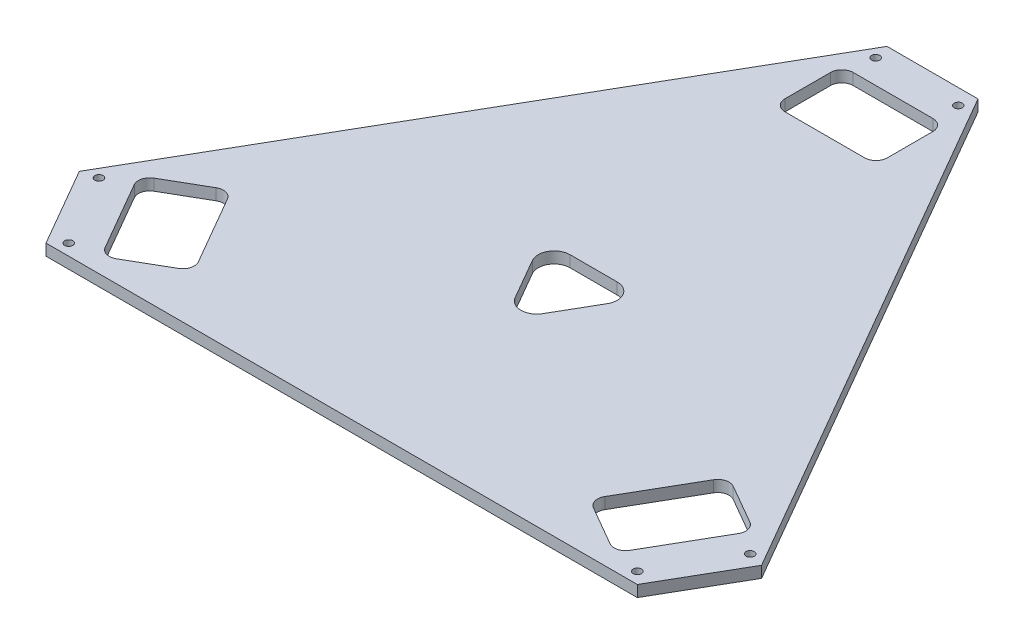
SolidWorks part; units mm, degrees
ref_plane "Plan de face" through (0, 0, 0) normal (0, 0, 1) x (1, 0, 0)
ref_plane "Plan de dessus" through (0, 0, 0) normal (0, 1, 0) x (1, 0, 0)
ref_plane "Plan de droite" through (0, 0, 0) normal (1, 0, 0) x (0, 0, -1)
sketch "Esquisse1" plane through (0, 0, 0) normal (0, 1, 0) x (1, 0, 0)
  line L0 (0, 15.1752) -> (0, -279.2734) construction
  line L1 (-32.5, -41.1164) -> (-137.5, -222.9818)
  line L2 (-105, -279.2734) -> (130, -279.2734)
  line L3 (137.5, -222.9818) -> (32.5, -41.1164)
  line L4 (0, 15.1752) -> (0, -134.8248) construction
  line L5 (135.3507, -233.2878) -> (86.8699, -257.259) construction
  line L7 (-32.5, -41.1164) -> (-20, -19.4658)
  line L13 (112.8507, -272.259) -> (109.3699, -218.2878) construction
  line L19 (-20, -19.4658) -> (20, -19.4658)
  line L21 (-137.5, -222.9818) -> (-150, -244.6324)
  line L22 (-105, -279.2734) -> (-130, -279.2734)
  line L24 (105, -279.2734) -> (-105, -279.2734)
  line L25 (32.5, -41.1164) -> (137.5, -222.9818)
  line L26 (-32.5, -41.1164) -> (0, 15.1752) construction
  line L27 (0, 15.1752) -> (32.5, -41.1164) construction
  line L28 (137.5, -222.9818) -> (170, -279.2734) construction
  line L29 (170, -279.2734) -> (105, -279.2734) construction
  line L30 (-105, -279.2734) -> (-170, -279.2734) construction
  line L31 (-170, -279.2734) -> (-137.5, -222.9818) construction
  line L32 (-170, -279.2734) -> (-35.7661, -201.7734) construction
  line L33 (-115.3507, -267.9289) -> (-132.8507, -237.618)
  line L34 (0, -279.2734) -> (0, -171.4176) construction
  line L35 (-108.5205, -269.759) -> (-91.2, -259.759)
  line L36 (-131.0205, -230.7878) -> (-113.7, -220.7878)
  line L37 (-89.3699, -252.9289) -> (-106.8699, -222.618)
  line L38 (-112.8507, -272.259) -> (-109.3699, -218.2878) construction
  line L39 (-135.3507, -233.2878) -> (-86.8699, -257.259) construction
  line L40 (-17.5, -66.8248) -> (17.5, -66.8248)
  line L41 (-22.5, -61.8248) -> (-22.5, -41.8248)
  line L42 (22.5, -61.8248) -> (22.5, -41.8248)
  line L43 (-17.5, -36.8248) -> (17.5, -36.8248)
  line L44 (-22.5, -66.8248) -> (22.5, -36.8248) construction
  line L45 (22.5, -66.8248) -> (-22.5, -36.8248) construction
  line L46 (135.3507, -233.2878) -> (86.8699, -257.259) construction
  line L47 (112.8507, -272.259) -> (109.3699, -218.2878) construction
  line L48 (170, -279.2734) -> (35.7661, -201.7734) construction
  line L49 (89.3699, -252.9289) -> (106.8699, -222.618)
  line L50 (131.0205, -230.7878) -> (113.7, -220.7878)
  line L51 (108.5205, -269.759) -> (91.2, -259.759)
  line L52 (115.3507, -267.9289) -> (132.8507, -237.618)
  line L53 (135.3507, -233.2878) -> (86.8699, -257.259) construction
  line L54 (112.8507, -272.259) -> (109.3699, -218.2878) construction
  line L55 (170, -279.2734) -> (35.7661, -201.7734) construction
  line L56 (170, -279.2734) -> (137.5, -222.9818) construction
  line L57 (105, -279.2734) -> (170, -279.2734) construction
  line L61 (89.3699, -252.9289) -> (106.8699, -222.618)
  line L62 (131.0205, -230.7878) -> (113.7, -220.7878)
  line L63 (108.5205, -269.759) -> (91.2, -259.759)
  line L64 (115.3507, -267.9289) -> (132.8507, -237.618)
  line L67 (-130, -279.2734) -> (-150, -244.6324)
  line L68 (32.5, -41.1164) -> (20, -19.4658)
  line L69 (170, -279.2734) -> (35.7661, -201.7734) construction
  line L70 (170, -279.2734) -> (137.5, -222.9818) construction
  line L71 (105, -279.2734) -> (170, -279.2734) construction
  line L72 (130, -279.2734) -> (150, -244.6324)
  line L73 (89.3699, -252.9289) -> (106.8699, -222.618)
  line L74 (131.0205, -230.7878) -> (113.7, -220.7878)
  line L75 (108.5205, -269.759) -> (91.2, -259.759)
  line L76 (115.3507, -267.9289) -> (132.8507, -237.618)
  line L77 (105, -279.2734) -> (130, -279.2734)
  line L78 (137.5, -222.9818) -> (150, -244.6324)
  line L79 (32.5, -41.1164) -> (137.5, -222.9818)
  arc A0 (131.0205, -230.7878) -> (132.8507, -237.618) centre (128.5205, -235.118) cw
  arc A1 (106.8699, -222.618) -> (113.7, -220.7878) centre (111.2, -225.118) cw
  arc A3 (17.5, -66.8248) -> (22.5, -61.8248) centre (17.5, -61.8248) ccw
  arc A4 (22.5, -41.8248) -> (17.5, -36.8248) centre (17.5, -41.8248) ccw
  arc A5 (-22.5, -41.8248) -> (-17.5, -36.8248) centre (-17.5, -41.8248) cw
  arc A6 (-22.5, -61.8248) -> (-17.5, -66.8248) centre (-17.5, -61.8248) ccw
  arc A7 (-91.2, -259.759) -> (-89.3699, -252.9289) centre (-93.7, -255.4289) ccw
  arc A8 (-108.5205, -269.759) -> (-115.3507, -267.9289) centre (-111.0205, -265.4289) cw
  arc A9 (-106.8699, -222.618) -> (-113.7, -220.7878) centre (-111.2, -225.118) ccw
  arc A10 (-131.0205, -230.7878) -> (-132.8507, -237.618) centre (-128.5205, -235.118) ccw
  arc A11 (131.0205, -230.7878) -> (132.8507, -237.618) centre (128.5205, -235.118) cw
  arc A12 (106.8699, -222.618) -> (113.7, -220.7878) centre (111.2, -225.118) cw
  arc A13 (108.5205, -269.759) -> (115.3507, -267.9289) centre (111.0205, -265.4289) ccw
  arc A14 (91.2, -259.759) -> (89.3699, -252.9289) centre (93.7, -255.4289) cw
  arc A18 (131.0205, -230.7878) -> (132.8507, -237.618) centre (128.5205, -235.118) cw
  arc A19 (106.8699, -222.618) -> (113.7, -220.7878) centre (111.2, -225.118) cw
  arc A20 (108.5205, -269.759) -> (115.3507, -267.9289) centre (111.0205, -265.4289) ccw
  arc A21 (91.2, -259.759) -> (89.3699, -252.9289) centre (93.7, -255.4289) cw
  arc A23 (108.5205, -269.759) -> (115.3507, -267.9289) centre (111.0205, -265.4289) ccw
  arc A24 (91.2, -259.759) -> (89.3699, -252.9289) centre (93.7, -255.4289) cw
  point P19 (0, -19.4658)
  point P32 (-111.1103, -245.2734)
  point P33 (0, -51.8248)
  point P88 (111.1103, -245.2734)
  dimension "D20" = 5
  dimension "D1" = 60
  dimension "D2" = 340
  dimension "D3" = 30
  dimension "D4" = 150
  dimension "D5" = 25
  dimension "D6" = 25
  dimension "D9" = 155
  dimension "D10" = 25
  dimension "D14" = 72
  dimension "D15" = 30
  dimension "D16" = 68
  dimension "D17" = 30
  dimension "D18" = 45
  dimension "D19" = 45
extrude "Boss.-Extru.1" add sketch "Esquisse1" along normal blind 5 contours L3 L1 L2 A10 L36 A9 L37 A7 L35 A8 L33 A6 L41 A5 L43 A4 L42 A3 L40 L51 A14 L49 A12 L50 A11 L52 A13 region at (0, 0, 181.1541)
sketch "Esquisse2" plane through (0, 5, 0) normal (0, 1, 0) x (1, 0, 0)
  line L0 (-150, -244.6324) -> (-145, -235.9721)
  line L7 (-150, -244.6324) -> (-141.3397, -249.6324)
  line L8 (0, -251.1744) -> (0, -66.8248) construction
  line L9 (-17.5, -66.8248) -> (17.5, -66.8248) construction
  line L23 (-145, -235.9721) -> (-136.3397, -240.9721)
  line L24 (-141.3397, -249.6324) -> (-136.3397, -240.9721)
  line L27 (-20, -19.4658) -> (-150, -244.6324) construction
  line L38 (-140, -261.9529) -> (-124.1007, -252.7734) construction
  line L50 (-130, -279.2734) -> (-150, -244.6324) construction
  line L85 (-115.3507, -267.9289) -> (-132.8507, -237.618) construction
  line L86 (-140.6699, -238.4721) -> (-145.6699, -247.1324) construction
  line L87 (-147.5, -240.3023) -> (-143.1699, -242.8023) construction
  line L88 (-125, -279.2734) -> (-125, -274.2734) construction
  line L89 (-120, -274.2734) -> (-130, -274.2734) construction
  line L90 (-130, -269.2734) -> (-120, -269.2734)
  line L91 (-120, -279.2734) -> (-120, -269.2734)
  line L92 (-130, -279.2734) -> (-130, -269.2734)
  line L93 (-130, -279.2734) -> (-120, -279.2734)
  line L94 (-20, -19.4658) -> (-25, -28.126)
  line L95 (-20, -19.4658) -> (-11.3397, -24.4658)
  line L108 (-25, -28.126) -> (-16.3397, -33.126)
  line L109 (-11.3397, -24.4658) -> (-16.3397, -33.126)
  line L110 (-150, -244.6324) -> (-20, -19.4658) construction
  line L111 (-15.6699, -21.9658) -> (-20.6699, -30.626) construction
  line L112 (-22.5, -23.7959) -> (-18.1699, -26.2959) construction
  line L113 (0, -19.4658) -> (0, -36.8248) construction
  line L114 (-20, -19.4658) -> (20, -19.4658) construction
  line L115 (-17.5, -36.8248) -> (17.5, -36.8248) construction
  line L116 (22.5, -23.7959) -> (18.1699, -26.2959) construction
  line L117 (15.6699, -21.9658) -> (20.6699, -30.626) construction
  line L118 (120, -274.2734) -> (130, -274.2734) construction
  line L119 (125, -279.2734) -> (125, -274.2734) construction
  line L120 (147.5, -240.3023) -> (143.1699, -242.8023) construction
  line L121 (140.6699, -238.4721) -> (145.6699, -247.1324) construction
  line L122 (140, -261.9529) -> (124.1007, -252.7734) construction
  line L123 (11.3397, -24.4658) -> (16.3397, -33.126)
  line L124 (25, -28.126) -> (16.3397, -33.126)
  line L125 (20, -19.4658) -> (11.3397, -24.4658)
  line L126 (20, -19.4658) -> (25, -28.126)
  line L127 (130, -279.2734) -> (120, -279.2734)
  line L128 (130, -279.2734) -> (130, -269.2734)
  line L129 (120, -279.2734) -> (120, -269.2734)
  line L130 (130, -269.2734) -> (120, -269.2734)
  line L131 (141.3397, -249.6324) -> (136.3397, -240.9721)
  line L132 (145, -235.9721) -> (136.3397, -240.9721)
  line L133 (150, -244.6324) -> (141.3397, -249.6324)
  line L134 (150, -244.6324) -> (145, -235.9721)
  dimension "D1" = 10
  dimension "D2" = 10
  dimension "D3" = 10
  dimension "D4" = 10
hole_wizard "Dégagement M31" positions "Esquisse3D1" profile "Esquisse4" hole size "M3" standard "BSI" end condition through all
sketch3d "Esquisse3D1"
  point P73 (-143.1699, 5, 242.8023)
  point P76 (-125, 5, 274.2734)
  point P79 (125, 5, 274.2734)
  point P82 (143.1699, 5, 242.8023)
  point P85 (-18.1699, 5, 26.2959)
  point P88 (18.1699, 5, 26.2959)
sketch "Esquisse4" plane through (-143.1699, 5, 242.8023) normal (1, 0, 0) x (0, 0, 1)
  line L0 (0, 0) -> (0, 5)
  line L1 (0, 5) -> (1.8, 5)
  line L2 (1.8, 5) -> (1.8, 0)
  line L5 (1.8, 0) -> (0, 0)
  line L11 (0, -6.35) -> (0, 107.95) construction
  dimension "Diamètre du perçage jusqu'au prochain" = 3.6
  dimension "Profondeur du perçage jusqu'au prochain" = 5
sketch "Esquisse6" plane through (0, 0, 0) normal (0, -1, 0) x (-1, 0, 0)
  line L0 (0, -19.4658) -> (0, -279.2734) construction
  line L6 (-140, -261.9529) -> (33.7923, -161.6139) construction
  line L7 (-16.4378, -178.9754) -> (-6.0622, -196.9466)
  line L9 (-130, -279.2734) -> (130, -279.2734) construction
  line L10 (6.0622, -196.9466) -> (16.4378, -178.9754)
  line L11 (10.3756, -168.4754) -> (-10.3756, -168.4754)
  line L12 (140, -261.9529) -> (0, -181.1239) construction
  line L13 (130, -279.2734) -> (150, -244.6324) construction
  circle A0 centre (0, -181.4658) radius 12.9904 construction
  arc A1 (-6.0622, -196.9466) -> (6.0622, -196.9466) centre (0, -193.4466) ccw
  arc A2 (16.4378, -178.9754) -> (10.3756, -168.4754) centre (10.3756, -175.4754) ccw
  arc A3 (-16.4378, -178.9754) -> (-10.3756, -168.4754) centre (-10.3756, -175.4754) cw
  point P13 (0, -207.4466)
  point P16 (22.5, -168.4754)
  point P19 (-22.5, -168.4754)
  dimension "D2" = 162
  dimension "D3" = 7
  dimension "D1" = 45
extrude "Enlèv. mat.-Extru.2" cut sketch "Esquisse6" against normal blind 10
